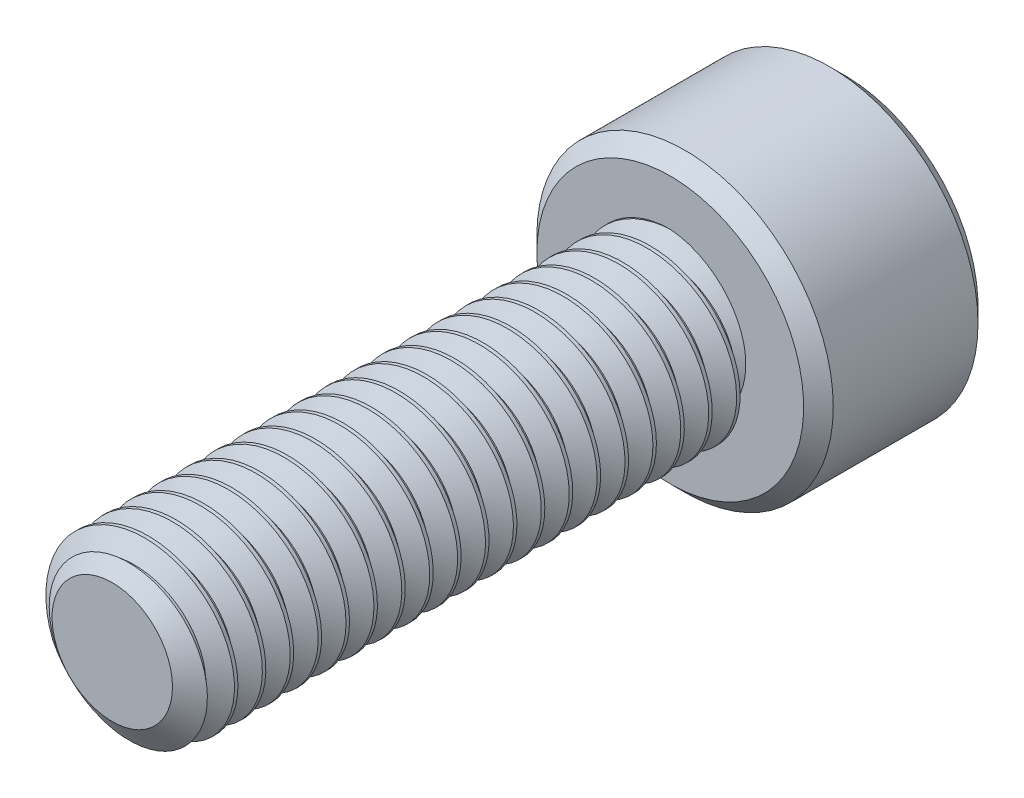
SolidWorks part; units mm, degrees
note: '?' marks a value the reader was unsure of.
other "DetailItem1"
ref_plane "Front Plane" through (0, 0, 0) normal (0, 0, 1) x (1, 0, 0)
ref_plane "Top Plane" through (0, 0, 0) normal (0, 1, 0) x (1, 0, 0)
ref_plane "Right Plane" through (0, 0, 0) normal (1, 0, 0) x (0, 0, -1)
sketch "Sketch1" plane through (0, 0, 0) normal (0, 0, 1) x (1, 0, 0)
  circle A0 centre (0, 0) radius 2.5
  dimension "OD" = 5
extrude "Extrude1" add sketch "Sketch1" against normal blind 16
sketch "Sketch2" plane through (0, 0, 0) normal (0, 0, 1) x (1, 0, 0)
  circle A0 centre (0, 0) radius 2.5 construction
  circle A1 centre (0, 0) radius 2.5
curve "Helix/Spiral1" pitch 0.8 height 16.8 turns 21 parameters "pitch"=0.8
sketch "Sketch3" plane through (0, 0, 0) normal (1, 0, 0) x (0, 0, -1)
  line L0 (-0.7, 2.5) -> (-0.4, 1.9804)
  line L1 (-0.4, 1.9804) -> (-0.3, 1.9804)
  line L2 (-0.3, 1.9804) -> (0, 2.5)
  line L3 (-0.7, 2.5) -> (0, 2.5)
  line L4 (-0.35, 2.5) -> (-0.35, 1.9804) construction
  line L5 (-0.55, 2.2402) -> (-0.15, 2.2402) construction
  line L6 (0, 2.5) -> (0, -2.5) construction
  dimension "D1" = 0.1
  dimension "D2" = 0.4
  dimension "D3" = 60
sweep "Cut-Sweep1" cut profiles "Sketch3" path "Helix/Spiral1"
sketch "Sketch4" plane through (0, 0, 0) normal (1, 0, 0) x (0, 0, -1)
  line L0 (0.5417, 2.5) -> (0, 1.7264)
  line L1 (0, 1.7264) -> (0, 2.5)
  line L2 (0.5417, 2.5) -> (0, 2.5)
  line L3 (-0.7, 2.5) -> (0, 2.5) construction
  line L4 (0, 0) -> (7.0209, 0) construction
  dimension "D1" = 55
  dimension "D2" = 0.254
revolve "Cut-Revolve1" cut sketch "Sketch4" angle 360 about L4
sketch "Sketch6" plane through (0, 0, -16) normal (0, 0, -1) x (-1, 0, 0)
  circle A0 centre (0, 0) radius 4.25
  dimension "head dia" = 8.5
extrude "Extrude2" add sketch "Sketch6" along normal blind 5
sketch "Sketch7" plane through (0, 0, -21) normal (0, 0, -1) x (-1, 0, 0)
  line L1 (0, 2.3094) -> (-2, 1.1547)
  line L2 (-2, 1.1547) -> (-2, -1.1547)
  line L3 (-2, -1.1547) -> (0, -2.3094)
  line L4 (0, -2.3094) -> (2, -1.1547)
  line L5 (2, -1.1547) -> (2, 1.1547)
  line L6 (2, 1.1547) -> (0, 2.3094)
  circle A0 centre (0, 0) radius 2 construction
  dimension "hex dia" = 4
extrude "Cut-Extrude1" cut sketch "Sketch7" against normal blind 3
sketch "Sketch8" plane through (0, 0, -21) normal (0, 0, -1) x (-1, 0, 0)
  circle A0 centre (0, 0) radius 2.3094
extrude "Cut-Extrude2" cut sketch "Sketch8" against normal through all draft 45
chamfer "Chamfer1" distance 0.425 angle 45 2 edges at (-4.25, 0, -21) (-4.25, 0, -16)
sketch "Sketch10" plane through (0, 0, -16) normal (0, 0, 1) x (1, 0, 0)
  circle A1 centre (0, 0) radius 2.5
  circle A2 centre (0, 0) radius 2.5
  dimension "D1" = 0
ref_plane "Plane1" through (0, 0, 0) normal (0, 0, 1) x (1, 0, 0)
extrude "partial thread" [suppressed] add sketch "Sketch10" along normal up to surface (36 mm away) separate body
chamfer "Chamfer2" [suppressed] distance 0.1 angle 45
combine bodies "Combine1" [suppressed] operation type? add bodies to combine 107 108
sketch "Sketch9" plane through (0, 0, 0) normal (1, 0, 0) x (0, 0, -1)
  line L0 (0, 2.5) -> (0, -2.5) construction
  line L1 (2, 2.5) -> (2, -2.5) construction
  dimension "D1" = 2
equation "\"D3@Helix/Spiral1\" = \"screw length@Extrude1\"+\"pitch@Helix/Spiral1\""
equation "\"D1@Sketch3\" = \"pitch@Helix/Spiral1\"*.125"
equation "\"D2@Sketch3\" = \"pitch@Helix/Spiral1\"*.5"
equation "\"D1@Cut-Extrude1\" = \"hex dia@Sketch7\"*.75"
equation "\"D1@Chamfer1\" = \"head dia@Sketch6\"*.05"
equation "\"D1@Sketch9\" = \"pitch@Helix/Spiral1\"*2.5"
equation "\"D1@Chamfer2\"=\"OD@Sketch1\"*.02"
